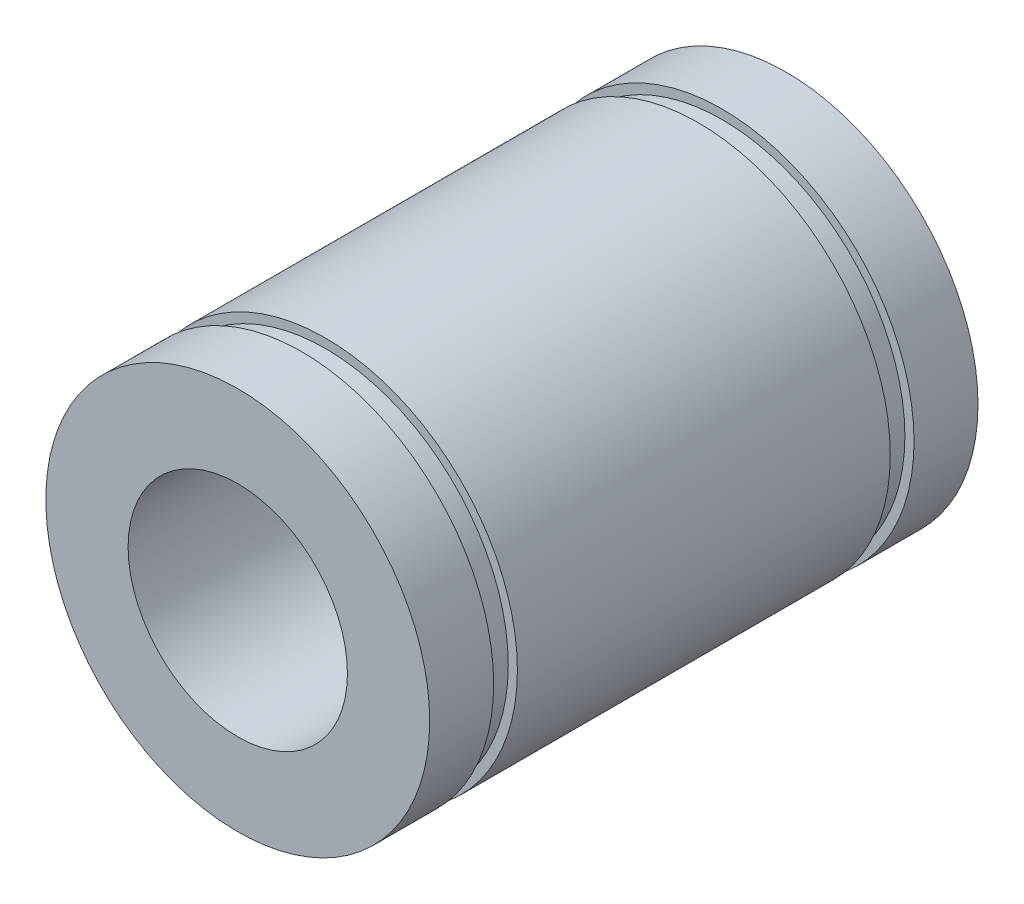
SolidWorks part; units mm, degrees
ref_plane "Front Plane" through (0, 0, 0) normal (0, 0, 1) x (1, 0, 0)
ref_plane "Top Plane" through (0, 0, 0) normal (0, 1, 0) x (1, 0, 0)
ref_plane "Right Plane" through (0, 0, 0) normal (1, 0, 0) x (0, 0, -1)
sketch "Sketch1" plane through (0, 0, 0) normal (0, 1, 0) x (1, 0, 0)
  line L0 (10.5, 0) -> (6, 0)
  line L1 (6, 0) -> (6, -30)
  line L2 (6, -30) -> (10.5, -30)
  line L3 (10.5, -30) -> (10.5, -26.5)
  line L4 (10.5, -26.5) -> (10, -26.5)
  line L5 (10, -26.5) -> (10, -25.2)
  line L6 (10, -25.2) -> (10.5, -25.2)
  line L7 (10.5, -25.2) -> (10.5, -4.8)
  line L8 (10.5, -4.8) -> (10, -4.8)
  line L9 (10, -4.8) -> (10, -3.5)
  line L10 (10, -3.5) -> (10.5, -3.5)
  line L11 (10.5, -3.5) -> (10.5, 0)
  line L12 (0, 0) -> (0, -30) construction
revolve "Revolve1" add sketch "Sketch1" angle 360 about L12 reverse direction yes
